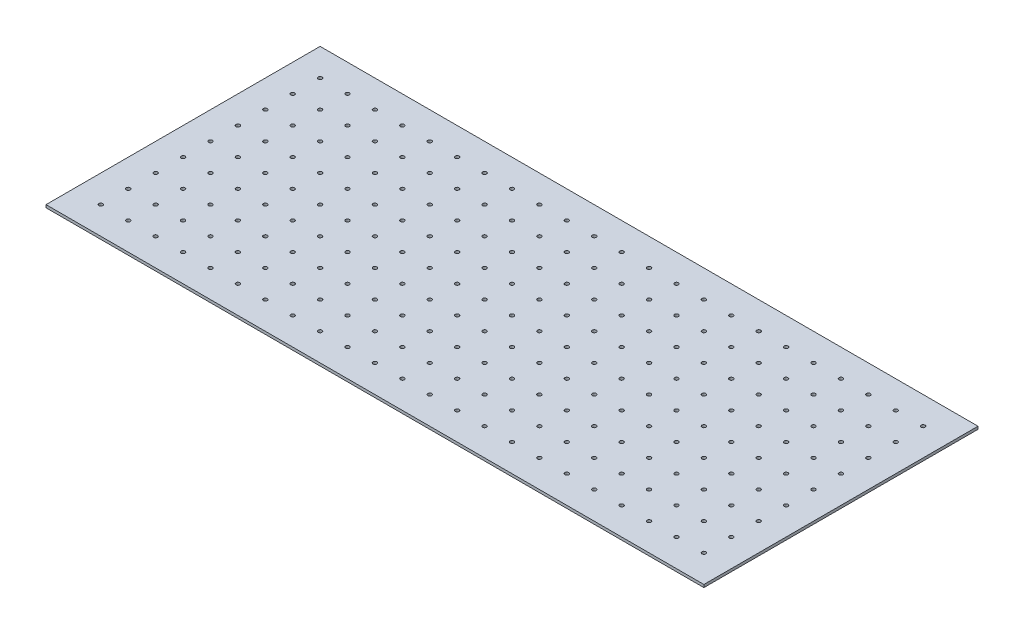
SolidWorks part; units mm, degrees
ref_plane "Alzado" through (0, 0, 0) normal (0, 0, 1) x (1, 0, 0)
ref_plane "Planta" through (0, 0, 0) normal (0, 1, 0) x (1, 0, 0)
ref_plane "Vista lateral" through (0, 0, 0) normal (1, 0, 0) x (0, 0, -1)
sketch "Croquis1" plane through (0, 0, 0) normal (0, 1, 0) x (1, 0, 0)
  line L1 (600, -250) -> (-600, -250)
  line L2 (600, -250) -> (600, 250)
  line L3 (600, 250) -> (-600, 250)
  line L4 (-600, -250) -> (-600, 250)
  line L5 (600, -250) -> (-600, 250) construction
  line L6 (600, 250) -> (-600, -250) construction
  point P0 (0, 0)
  dimension "D1" = 500
  dimension "D2" = 1200
extrude "Saliente-Extruir1" add sketch "Croquis1" along normal blind 5
sketch "Croquis3" plane through (0, 5, 0) normal (0, 1, 0) x (1, 0, 0)
  line L0 (-550, 200) -> (-550, 250) construction
  line L1 (600, 250) -> (-600, 250) construction
  line L2 (-550, 200) -> (-600, 200) construction
  line L3 (-600, 250) -> (-600, -250) construction
  circle A0 centre (-550, 200) radius 3.5
  point P9 (-575.5553, 228.2177)
  dimension "D1" = 7
  dimension "D2" = 50
  dimension "D3" = 50
extrude "Cortar-Extruir2" cut sketch "Croquis3" against normal through all
pattern_linear "MatrizL1" count 23 spacing 50 along (1, 0, 0) count 9 spacing 50 along (0, 0, 1) of "Cortar-Extruir2"
